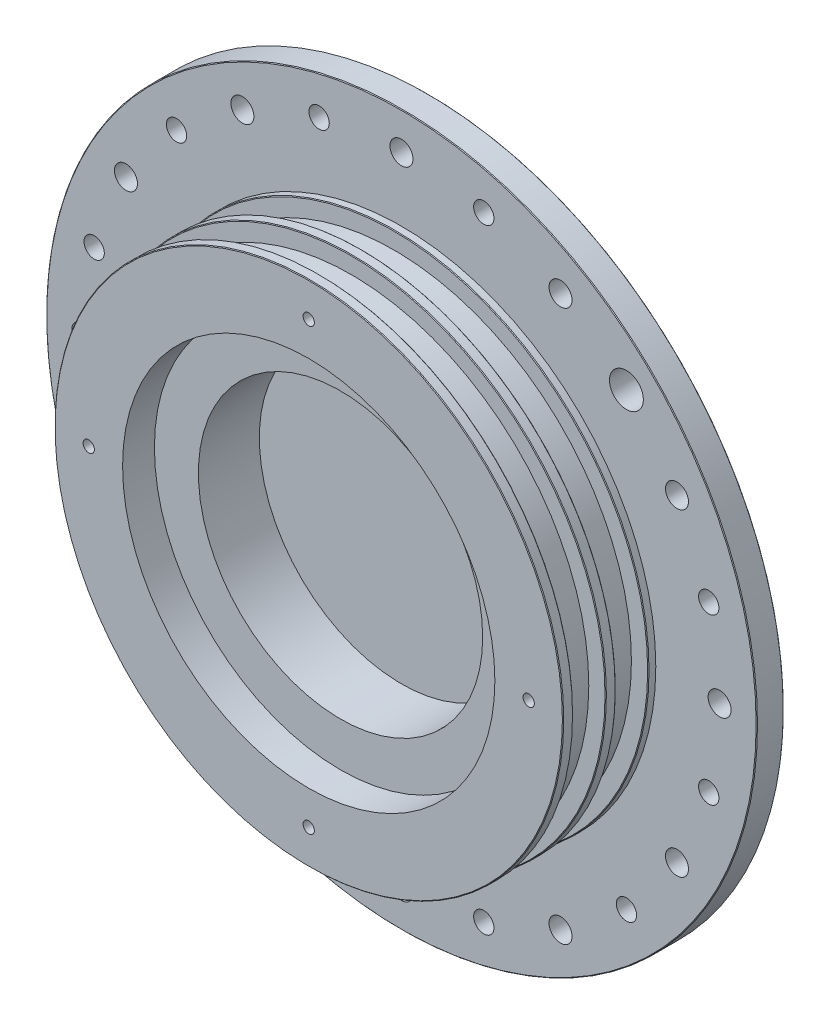
SolidWorks part; units mm, degrees
other "Marquage1"
sketch "Esquisse22" plane through (-100, 100, -114.225) normal (-0.6969, 0.6451, 0.3132) x (0.5706, 0.7634, -0.3027)
sketch "Esquisse26" plane through (-110, 110, -114.225) normal (-0.6969, 0.6451, 0.3132) x (0.5706, 0.7634, -0.3027)
sketch "Esquisse28" plane through (-110, 110, -114.225) normal (-0.6969, 0.6451, 0.3132) x (0.5706, 0.7634, -0.3027)
sketch "Esquisse31" plane through (-110, 110, -114.225) normal (-0.6969, 0.6451, 0.3132) x (0.5706, 0.7634, -0.3027)
sketch "Esquisse32" plane through (-100, 100, -114.225) normal (-0.6969, 0.6451, 0.3132) x (0.5706, 0.7634, -0.3027)
material "AISI 316 Barre d'acier inoxydable recuit (SS)"
ref_plane "Plan de face" through (0, 0, 0) normal (0, 0, 1) x (1, 0, 0)
ref_plane "Plan de dessus" through (0, 0, 0) normal (0, 1, 0) x (1, 0, 0)
ref_plane "Plan de droite" through (0, 0, 0) normal (1, 0, 0) x (0, 0, -1)
sketch "Esquisse1" plane through (0, 0, 0) normal (0, 1, 0) x (1, 0, 0)
  line L0 (87.5, 35.4) -> (0, 35.4)
  line L1 (0, 35.4) -> (0, 0)
  line L2 (0, 0) -> (75.15, 0)
  line L3 (75.15, 0) -> (75.15, 3)
  line L4 (75.15, 3) -> (70.15, 3)
  line L5 (70.15, 3) -> (70.15, 12.6)
  line L6 (70.15, 12.6) -> (75.15, 12.6)
  line L7 (75.15, 12.6) -> (75.15, 15.6)
  line L8 (75.15, 15.6) -> (70.15, 15.6)
  line L9 (70.15, 15.6) -> (70.15, 25.2)
  line L10 (70.15, 25.2) -> (75.15, 25.2)
  line L11 (75.15, 25.2) -> (75.15, 27.4)
  line L12 (75.15, 27.4) -> (87.5, 27.4)
  line L13 (87.5, 27.4) -> (87.5, 35.4)
  line L14 (0, 35.4) -> (0, 0) construction
  dimension "D1" = 8
  dimension "D2" = 2.2
  dimension "D3" = 9.6
  dimension "D4" = 3
  dimension "D5" = 9.6
  dimension "D6" = 3
  dimension "D7" = 5
  dimension "D8" = 75.15
  dimension "D9" = 87.5
revolve "Révolution1" add sketch "Esquisse1" angle 360 about L14 reverse direction yes
hole_wizard "Diamètre du perçage Ø9.0 (9)1" positions "Esquisse3" profile "Esquisse2" hole size "Ø9.0" standard "Ansi Metric"
sketch "Esquisse3" plane through (0, 0, -27.4) normal (0, 0, 1) x (1, 0, 0)
  point P0 (-87.5, 0)
  point P1 (0, 87.5)
  point P2 (0, -87.5)
  point P3 (87.5, 0)
sketch "Esquisse2" plane through (-87.5, 0, -27.4) normal (1, 0, 0) x (0, -1, 0)
  line L0 (0, 0) -> (0, 3)
  line L1 (0, 3) -> (4.5, 3)
  line L2 (4.5, 3) -> (4.5, 0)
  line L5 (4.5, 0) -> (0, 0)
  line L10 (0, 3) -> (-4.5, 3) construction
  line L11 (0, -6.35) -> (0, 107.95) construction
  dimension "Diamètre du perçage" = 9
  dimension "Profondeur du perçage" = 3
  dimension "Angle de pointe" = 180
hole_wizard "Dégagement M31" positions "Esquisse5" profile "Esquisse4" hole size "M3" standard "Ansi Metric"
sketch "Esquisse5" plane through (0, 0, 0) normal (0, 0, 1) x (1, 0, 0)
  point P0 (-65, 0)
  point P1 (65, 0)
  point P2 (0, 65)
  point P3 (0, -65)
sketch "Esquisse4" plane through (-65, 0, 0) normal (1, 0, 0) x (0, -1, 0)
  line L0 (0, 0) -> (0, 17.001)
  line L1 (0, 17.001) -> (1.666, 16)
  line L2 (1.666, 16) -> (1.666, 0)
  line L5 (1.666, 0) -> (0, 0)
  line L10 (0, 17.001) -> (-1.666, 16) construction
  line L11 (0, -6.35) -> (0, 107.95) construction
  dimension "Diamètre du perçage" = 3.332
  dimension "Profondeur du perçage" = 16
  dimension "Angle de pointe" = 118
hole_wizard "Dégagement M1001" positions "Esquisse7" profile "Esquisse6" hole size "M100" standard "Ansi Metric"
sketch "Esquisse7" plane through (0, 0, 0) normal (0, 0, 1) x (1, 0, 0)
  point P0 (0, 0)
sketch "Esquisse6" plane through (0, 0, 0) normal (1, 0, 0) x (0, -1, 0)
  line L0 (0, 0) -> (0, 27.4)
  line L1 (0, 27.4) -> (55, 27.4)
  line L2 (55, 27.4) -> (55, 0)
  line L5 (55, 0) -> (0, 0)
  line L10 (0, 27.4) -> (-55, 27.4) construction
  line L11 (0, -6.35) -> (0, 107.95) construction
  dimension "Diamètre du perçage" = 110
  dimension "Profondeur du perçage" = 27.4
  dimension "Angle de pointe" = 180
sketch "Esquisse8" plane through (0, 0, -35.4) normal (0, 0, -1) x (-1, 0, 0)
  line L0 (0, 0) -> (0, -108.9201) construction
  circle A0 centre (0, 0) radius 108.9201 construction
  circle A1 centre (0, 0) radius 105
  circle A2 centre (0, 0) radius 77.5
  circle A3 centre (0, 0) radius 87.5 construction
  dimension "D2" = 10
  dimension "D1" = 210
extrude "Boss.-Extru.1" add sketch "Esquisse8" against normal blind 8
ref_plane "Plan1" through (0, -105, 0) normal (0, -1, 0) x (-1, 0, 0)
sketch "Esquisse9" plane through (0, 0, -35.4) normal (0, 0, 1) x (1, 0, 0)
  line L0 (0, -50) -> (0, 0) construction
  circle A0 centre (0, -50) radius 3.4
  circle A17 centre (0, -94) radius 3.4
  circle A18 centre (-25, -43.3013) radius 3.4
  circle A19 centre (-47, -81.4064) radius 3.4
  circle A20 centre (-43.3013, -25) radius 3.4
  circle A21 centre (-81.4064, -47) radius 3.4
  circle A22 centre (-50, 0) radius 3.4
  circle A23 centre (-94, 0) radius 3.4
  circle A24 centre (-43.3013, 25) radius 3.4
  circle A25 centre (-81.4064, 47) radius 3.4
  circle A26 centre (-25, 43.3013) radius 3.4
  circle A27 centre (-47, 81.4064) radius 3.4
  circle A28 centre (0, 50) radius 3.4
  circle A29 centre (0, 94) radius 3.4
  circle A30 centre (25, 43.3013) radius 3.4
  circle A31 centre (47, 81.4064) radius 3.4
  circle A32 centre (43.3013, 25) radius 3.4
  circle A33 centre (81.4064, 47) radius 3.4
  circle A34 centre (50, 0) radius 3.4
  circle A35 centre (94, 0) radius 3.4
  circle A36 centre (43.3013, -25) radius 3.4
  circle A37 centre (81.4064, -47) radius 3.4
  circle A38 centre (25, -43.3013) radius 3.4
  circle A39 centre (47, -81.4064) radius 3.4
  point P17 (0, 0)
  point P28 (0, 0)
  point P31 (0, 0)
  point P55 (0, 0)
  dimension "D1" = 6.8
  dimension "D3" = 94
  dimension "D2" = 50
extrude "Enlèv. mat.-Extru.1" cut sketch "Esquisse9" along normal blind 20
sketch "Esquisse24" plane through (0, 0, -35.4) normal (0, 0, -1) x (-1, 0, 0)
  line L0 (28.0621, 104.7291) -> (0, 0) construction
  line L1 (-54.2118, 93.8976) -> (0, 0) construction
  line L2 (0, 0) -> (0, 94) construction
  line L3 (0, 0) -> (-66.468, 66.468) construction
  circle A0 centre (-47, 81.4064) radius 5 construction
  circle A1 centre (24.329, 90.797) radius 3
  circle A2 centre (66.468, 66.468) radius 3
  circle A3 centre (90.797, 24.329) radius 3
  circle A4 centre (90.797, -24.329) radius 3
  circle A5 centre (-14, 24.2487) radius 5
  circle A6 centre (7.2469, 27.0459) radius 5
  circle A7 centre (24.2487, 14) radius 5
  circle A8 centre (27.0459, -7.2469) radius 5
  circle A9 centre (14, -24.2487) radius 5
  circle A10 centre (-7.2469, -27.0459) radius 5
  circle A11 centre (-24.2487, -14) radius 5
  circle A12 centre (-27.0459, 7.2469) radius 5
  circle A13 centre (-66.468, 66.468) radius 5
  circle A14 centre (66.468, -66.468) radius 3
  circle A15 centre (24.329, -90.797) radius 3
  circle A16 centre (-24.329, -90.797) radius 3
  circle A17 centre (-66.468, -66.468) radius 3
  circle A18 centre (-90.797, -24.329) radius 3
  circle A19 centre (-90.797, 24.329) radius 3
  circle A20 centre (-66.468, 66.468) radius 3 construction
  circle A21 centre (-24.329, 90.797) radius 3
  circle A22 centre (0, 0) radius 82.55 construction
  circle A23 centre (-66.468, 66.468) radius 8 construction
  circle A24 centre (0, 0) radius 5
  point P19 (0, 0)
  point P36 (0, 0)
  dimension "D1" = 6
  dimension "D3" = 10
  dimension "D6" = 10
  dimension "D11" = 15
  dimension "D12" = 10
  dimension "D14" = 165.1
  dimension "D15" = 16
  dimension "D2" = 94
  dimension "D4" = 94
  dimension "D7" = 28
  dimension "D9" = 45
  dimension "D10" = 15
  dimension "D13" = 94
  dimension "D5" = 12
  dimension "D8" = 8
extrude "Enlèv. mat.-Extru.15" cut sketch "Esquisse24" against normal through all and the other way through all
chamfer "Chanfrein1" distance 0.2 angle 45 7 edges at (75.15, 0, -25.2) (75.15, 0, -3) (75.15, 0, -12.6) (75.15, 0, -15.6) (-105, 0, -35.4) (-105, 0, -27.4) (75.15, 0, 0)
sketch "Esquisse25" plane through (0, 0, -35.4) normal (0, 0, -1) x (-1, 0, 0)
  line L0 (-24.9287, -1.7061) -> (-33.3561, 0.552) construction
  line L1 (-33.3561, 0.552) -> (-29.1632, 16.2) construction
  line L2 (-29.1632, 16.2) -> (-20.7358, 13.9419) construction
  line L3 (-20.7358, 13.9419) -> (-24.9287, -1.7061) construction
  line L4 (0, 0) -> (-31.2596, 8.376) construction
  line L5 (-27.0459, 7.2469) -> (-33.914, -18.3852) construction
  line L6 (-22.5347, 14.4239) -> (-27.3643, 15.718)
  line L7 (-26.7275, -1.2241) -> (-31.5572, 0.07)
  line L8 (-5.7352, 26.1336) -> (-8.2352, 30.4638)
  line L9 (-19.7648, 18.0336) -> (-22.2648, 22.3638)
  line L10 (14.4239, 22.5347) -> (15.718, 27.3643)
  line L11 (-1.2241, 26.7275) -> (0.07, 31.5572)
  line L12 (26.1336, 5.7352) -> (30.4638, 8.2352)
  line L13 (18.0336, 19.7648) -> (22.3638, 22.2648)
  line L14 (22.5347, -14.4239) -> (27.3643, -15.718)
  line L15 (26.7275, 1.2241) -> (31.5572, -0.07)
  line L16 (5.7352, -26.1336) -> (8.2352, -30.4638)
  line L17 (19.7648, -18.0336) -> (22.2648, -22.3638)
  line L18 (-14.4239, -22.5347) -> (-15.718, -27.3643)
  line L19 (1.2241, -26.7275) -> (-0.07, -31.5572)
  line L20 (-26.1336, -5.7352) -> (-30.4638, -8.2352)
  line L21 (-18.0336, -19.7648) -> (-22.3638, -22.2648)
  circle A0 centre (0, 0) radius 9.2
  arc A2 (-33.3561, 0.552) -> (-29.1632, 16.2) centre (-27.0459, 7.2469) cw construction
  arc A3 (-24.9287, -1.7061) -> (-20.7358, 13.9419) centre (-27.0459, 7.2469) ccw construction
  arc A4 (-22.8033, -0.9164) -> (-19.29, 12.1953) centre (-27.0459, 7.2469) ccw
  arc A5 (-19.29, 12.1953) -> (-19.4952, 12.5745) centre (-16.7609, 13.8089) cw
  arc A6 (-19.4952, 12.5745) -> (-21.9939, 14.3309) centre (-22.2295, 11.3402) ccw
  arc A7 (-21.9939, 14.3309) -> (-22.5347, 14.4239) centre (-21.7582, 17.3217) cw
  arc A8 (-27.8791, 15.9079) -> (-27.3643, 15.718) centre (-26.5878, 18.6158) ccw
  arc A9 (-30.9212, 15.6361) -> (-27.8791, 15.9079) centre (-29.1704, 13.2) cw
  arc A10 (-31.2885, 15.4103) -> (-30.9212, 15.6361) centre (-32.672, 18.0722) ccw
  arc A11 (-34.8018, 2.2986) -> (-31.2885, 15.4103) centre (-27.0459, 7.2469) cw
  arc A12 (-34.8018, 2.2986) -> (-34.5966, 1.9193) centre (-37.3309, 0.685) cw
  arc A13 (-34.5966, 1.9193) -> (-32.098, 0.1629) centre (-31.8623, 3.1537) ccw
  arc A14 (-32.098, 0.1629) -> (-31.5572, 0.07) centre (-32.3336, -2.8278) cw
  arc A15 (-26.2127, -1.414) -> (-26.7275, -1.2241) centre (-27.504, -4.1219) ccw
  arc A16 (-23.1707, -1.1423) -> (-26.2127, -1.414) centre (-24.9215, 1.2939) cw
  arc A17 (-22.8033, -0.9164) -> (-23.1707, -1.1423) centre (-21.4198, -3.5784) ccw
  arc A19 (-22.9833, 26.2339) -> (-11.2276, 33.0211) centre (-14, 24.2487) cw
  arc A20 (-11.2276, 33.0211) -> (-10.8082, 32.921) centre (-10.3236, 35.8816) ccw
  arc A21 (-10.8082, 32.921) -> (-8.4649, 30.9621) centre (-11.2928, 29.9604) cw
  arc A22 (-8.4649, 30.9621) -> (-8.2352, 30.4638) centre (-5.6371, 31.9638) ccw
  arc A23 (-5.4185, 25.6855) -> (-5.7352, 26.1336) centre (-3.1371, 27.6336) cw
  arc A24 (-4.8937, 22.6768) -> (-5.4185, 25.6855) centre (-7.6999, 23.7374) ccw
  arc A25 (-5.0167, 22.2635) -> (-4.8937, 22.6768) centre (-2.0874, 21.6161) cw
  arc A26 (-16.7724, 15.4764) -> (-5.0167, 22.2635) centre (-14, 24.2487) ccw
  arc A27 (-16.7724, 15.4764) -> (-17.1918, 15.5764) centre (-17.6764, 12.6158) ccw
  arc A28 (-17.1918, 15.5764) -> (-19.5351, 17.5353) centre (-16.7072, 18.537) cw
  arc A29 (-19.5351, 17.5353) -> (-19.7648, 18.0336) centre (-22.3629, 16.5336) ccw
  arc A30 (-22.5815, 22.8119) -> (-22.2648, 22.3638) centre (-24.8629, 20.8638) cw
  arc A31 (-23.1063, 25.8207) -> (-22.5815, 22.8119) centre (-20.3001, 24.76) ccw
  arc A32 (-22.9833, 26.2339) -> (-23.1063, 25.8207) centre (-25.9126, 26.8813) cw
  arc A33 (2.2986, 34.8018) -> (15.4103, 31.2885) centre (7.2469, 27.0459) cw
  arc A34 (15.4103, 31.2885) -> (15.6361, 30.9212) centre (18.0722, 32.672) ccw
  arc A35 (15.6361, 30.9212) -> (15.9079, 27.8791) centre (13.2, 29.1704) cw
  arc A36 (15.9079, 27.8791) -> (15.718, 27.3643) centre (18.6158, 26.5878) ccw
  arc A37 (14.3309, 21.9939) -> (14.4239, 22.5347) centre (17.3217, 21.7582) cw
  arc A38 (12.5745, 19.4952) -> (14.3309, 21.9939) centre (11.3402, 22.2295) ccw
  arc A39 (12.1953, 19.29) -> (12.5745, 19.4952) centre (13.8089, 16.7609) cw
  arc A40 (-0.9164, 22.8033) -> (12.1953, 19.29) centre (7.2469, 27.0459) ccw
  arc A41 (-0.9164, 22.8033) -> (-1.1423, 23.1707) centre (-3.5784, 21.4198) ccw
  arc A42 (-1.1423, 23.1707) -> (-1.414, 26.2127) centre (1.2939, 24.9215) cw
  arc A43 (-1.414, 26.2127) -> (-1.2241, 26.7275) centre (-4.1219, 27.504) ccw
  arc A44 (0.1629, 32.098) -> (0.07, 31.5572) centre (-2.8278, 32.3336) cw
  arc A45 (1.9193, 34.5966) -> (0.1629, 32.098) centre (3.1537, 31.8623) ccw
  arc A46 (2.2986, 34.8018) -> (1.9193, 34.5966) centre (0.685, 37.3309) cw
  arc A47 (26.2339, 22.9833) -> (33.0211, 11.2276) centre (24.2487, 14) cw
  arc A48 (33.0211, 11.2276) -> (32.921, 10.8082) centre (35.8816, 10.3236) ccw
  arc A49 (32.921, 10.8082) -> (30.9621, 8.4649) centre (29.9604, 11.2928) cw
  arc A50 (30.9621, 8.4649) -> (30.4638, 8.2352) centre (31.9638, 5.6371) ccw
  arc A51 (25.6855, 5.4185) -> (26.1336, 5.7352) centre (27.6336, 3.1371) cw
  arc A52 (22.6768, 4.8937) -> (25.6855, 5.4185) centre (23.7374, 7.6999) ccw
  arc A53 (22.2635, 5.0167) -> (22.6768, 4.8937) centre (21.6161, 2.0874) cw
  arc A54 (15.4764, 16.7724) -> (22.2635, 5.0167) centre (24.2487, 14) ccw
  arc A55 (15.4764, 16.7724) -> (15.5764, 17.1918) centre (12.6158, 17.6764) ccw
  arc A56 (15.5764, 17.1918) -> (17.5353, 19.5351) centre (18.537, 16.7072) cw
  arc A57 (17.5353, 19.5351) -> (18.0336, 19.7648) centre (16.5336, 22.3629) ccw
  arc A58 (22.8119, 22.5815) -> (22.3638, 22.2648) centre (20.8638, 24.8629) cw
  arc A59 (25.8207, 23.1063) -> (22.8119, 22.5815) centre (24.76, 20.3001) ccw
  arc A60 (26.2339, 22.9833) -> (25.8207, 23.1063) centre (26.8813, 25.9126) cw
  arc A61 (34.8018, -2.2986) -> (31.2885, -15.4103) centre (27.0459, -7.2469) cw
  arc A62 (31.2885, -15.4103) -> (30.9212, -15.6361) centre (32.672, -18.0722) ccw
  arc A63 (30.9212, -15.6361) -> (27.8791, -15.9079) centre (29.1704, -13.2) cw
  arc A64 (27.8791, -15.9079) -> (27.3643, -15.718) centre (26.5878, -18.6158) ccw
  arc A65 (21.9939, -14.3309) -> (22.5347, -14.4239) centre (21.7582, -17.3217) cw
  arc A66 (19.4952, -12.5745) -> (21.9939, -14.3309) centre (22.2295, -11.3402) ccw
  arc A67 (19.29, -12.1953) -> (19.4952, -12.5745) centre (16.7609, -13.8089) cw
  arc A68 (22.8033, 0.9164) -> (19.29, -12.1953) centre (27.0459, -7.2469) ccw
  arc A69 (22.8033, 0.9164) -> (23.1707, 1.1423) centre (21.4198, 3.5784) ccw
  arc A70 (23.1707, 1.1423) -> (26.2127, 1.414) centre (24.9215, -1.2939) cw
  arc A71 (26.2127, 1.414) -> (26.7275, 1.2241) centre (27.504, 4.1219) ccw
  arc A72 (32.098, -0.1629) -> (31.5572, -0.07) centre (32.3336, 2.8278) cw
  arc A73 (34.5966, -1.9193) -> (32.098, -0.1629) centre (31.8623, -3.1537) ccw
  arc A74 (34.8018, -2.2986) -> (34.5966, -1.9193) centre (37.3309, -0.685) cw
  arc A75 (22.9833, -26.2339) -> (11.2276, -33.0211) centre (14, -24.2487) cw
  arc A76 (11.2276, -33.0211) -> (10.8082, -32.921) centre (10.3236, -35.8816) ccw
  arc A77 (10.8082, -32.921) -> (8.4649, -30.9621) centre (11.2928, -29.9604) cw
  arc A78 (8.4649, -30.9621) -> (8.2352, -30.4638) centre (5.6371, -31.9638) ccw
  arc A79 (5.4185, -25.6855) -> (5.7352, -26.1336) centre (3.1371, -27.6336) cw
  arc A80 (4.8937, -22.6768) -> (5.4185, -25.6855) centre (7.6999, -23.7374) ccw
  arc A81 (5.0167, -22.2635) -> (4.8937, -22.6768) centre (2.0874, -21.6161) cw
  arc A82 (16.7724, -15.4764) -> (5.0167, -22.2635) centre (14, -24.2487) ccw
  arc A83 (16.7724, -15.4764) -> (17.1918, -15.5764) centre (17.6764, -12.6158) ccw
  arc A84 (17.1918, -15.5764) -> (19.5351, -17.5353) centre (16.7072, -18.537) cw
  arc A85 (19.5351, -17.5353) -> (19.7648, -18.0336) centre (22.3629, -16.5336) ccw
  arc A86 (22.5815, -22.8119) -> (22.2648, -22.3638) centre (24.8629, -20.8638) cw
  arc A87 (23.1063, -25.8207) -> (22.5815, -22.8119) centre (20.3001, -24.76) ccw
  arc A88 (22.9833, -26.2339) -> (23.1063, -25.8207) centre (25.9126, -26.8813) cw
  arc A89 (-2.2986, -34.8018) -> (-15.4103, -31.2885) centre (-7.2469, -27.0459) cw
  arc A90 (-15.4103, -31.2885) -> (-15.6361, -30.9212) centre (-18.0722, -32.672) ccw
  arc A91 (-15.6361, -30.9212) -> (-15.9079, -27.8791) centre (-13.2, -29.1704) cw
  arc A92 (-15.9079, -27.8791) -> (-15.718, -27.3643) centre (-18.6158, -26.5878) ccw
  arc A93 (-14.3309, -21.9939) -> (-14.4239, -22.5347) centre (-17.3217, -21.7582) cw
  arc A94 (-12.5745, -19.4952) -> (-14.3309, -21.9939) centre (-11.3402, -22.2295) ccw
  arc A95 (-12.1953, -19.29) -> (-12.5745, -19.4952) centre (-13.8089, -16.7609) cw
  arc A96 (0.9164, -22.8033) -> (-12.1953, -19.29) centre (-7.2469, -27.0459) ccw
  arc A97 (0.9164, -22.8033) -> (1.1423, -23.1707) centre (3.5784, -21.4198) ccw
  arc A98 (1.1423, -23.1707) -> (1.414, -26.2127) centre (-1.2939, -24.9215) cw
  arc A99 (1.414, -26.2127) -> (1.2241, -26.7275) centre (4.1219, -27.504) ccw
  arc A100 (-0.1629, -32.098) -> (-0.07, -31.5572) centre (2.8278, -32.3336) cw
  arc A101 (-1.9193, -34.5966) -> (-0.1629, -32.098) centre (-3.1537, -31.8623) ccw
  arc A102 (-2.2986, -34.8018) -> (-1.9193, -34.5966) centre (-0.685, -37.3309) cw
  arc A103 (-26.2339, -22.9833) -> (-33.0211, -11.2276) centre (-24.2487, -14) cw
  arc A104 (-33.0211, -11.2276) -> (-32.921, -10.8082) centre (-35.8816, -10.3236) ccw
  arc A105 (-32.921, -10.8082) -> (-30.9621, -8.4649) centre (-29.9604, -11.2928) cw
  arc A106 (-30.9621, -8.4649) -> (-30.4638, -8.2352) centre (-31.9638, -5.6371) ccw
  arc A107 (-25.6855, -5.4185) -> (-26.1336, -5.7352) centre (-27.6336, -3.1371) cw
  arc A108 (-22.6768, -4.8937) -> (-25.6855, -5.4185) centre (-23.7374, -7.6999) ccw
  arc A109 (-22.2635, -5.0167) -> (-22.6768, -4.8937) centre (-21.6161, -2.0874) cw
  arc A110 (-15.4764, -16.7724) -> (-22.2635, -5.0167) centre (-24.2487, -14) ccw
  arc A111 (-15.4764, -16.7724) -> (-15.5764, -17.1918) centre (-12.6158, -17.6764) ccw
  arc A112 (-15.5764, -17.1918) -> (-17.5353, -19.5351) centre (-18.537, -16.7072) cw
  arc A113 (-17.5353, -19.5351) -> (-18.0336, -19.7648) centre (-16.5336, -22.3629) ccw
  arc A114 (-22.8119, -22.5815) -> (-22.3638, -22.2648) centre (-20.8638, -24.8629) cw
  arc A115 (-25.8207, -23.1063) -> (-22.8119, -22.5815) centre (-24.76, -20.3001) ccw
  arc A116 (-26.2339, -22.9833) -> (-25.8207, -23.1063) centre (-26.8813, -25.9126) cw
  point P7 (-22.8322, 6.1179)
  point P35 (-24.9495, 15.0709)
  point P250 (0, 0)
  dimension "D1" = 9.2
  dimension "D3" = 3
  dimension "D4" = 2.5
  dimension "D2" = 16.2
  dimension "D5" = 8
extrude "Enlèv. mat.-Extru.18" cut sketch "Esquisse25" against normal blind 2
sketch "Esquisse35" plane through (0, 0, -27.4) normal (0, 0, 1) x (1, 0, 0)
  circle A0 centre (0, 0) radius 55
  circle A1 centre (0, 0) radius 42
  circle A4 centre (0, 0) radius 55 construction
  dimension "D1" = 84
extrude "Boss.-Extru.4" add sketch "Esquisse35" along normal blind 18
sketch "Esquisse36" plane through (0, 0, -27.4) normal (0, 0, 1) x (1, 0, 0)
  circle A0 centre (-27.0459, -7.2469) radius 5
  circle A1 centre (-27.0459, -7.2469) radius 5 construction
  circle A2 centre (-24.2487, 14) radius 5
  circle A3 centre (-7.2469, 27.0459) radius 5
  circle A4 centre (14, 24.2487) radius 5
  circle A5 centre (27.0459, 7.2469) radius 5
  circle A6 centre (24.2487, -14) radius 5
  circle A7 centre (7.2469, -27.0459) radius 5
  circle A8 centre (-14, -24.2487) radius 5
  circle A9 centre (0, 0) radius 5
  circle A11 centre (0, 0) radius 5 construction
  point P14 (0, 0)
  dimension "D1" = 8
extrude "Boss.-Extru.5" add sketch "Esquisse36" against normal blind 4
extrude "Enlèv. mat.-Extru.20" cut sketch "Esquisse9<2>" along normal blind 20
sketch "Esquisse9<2>" plane through (0, 0, -35.4) normal (0, 0, 1) x (1, 0, 0) same geometry as "Esquisse9"
equation "\"_à\"=76.5769"
